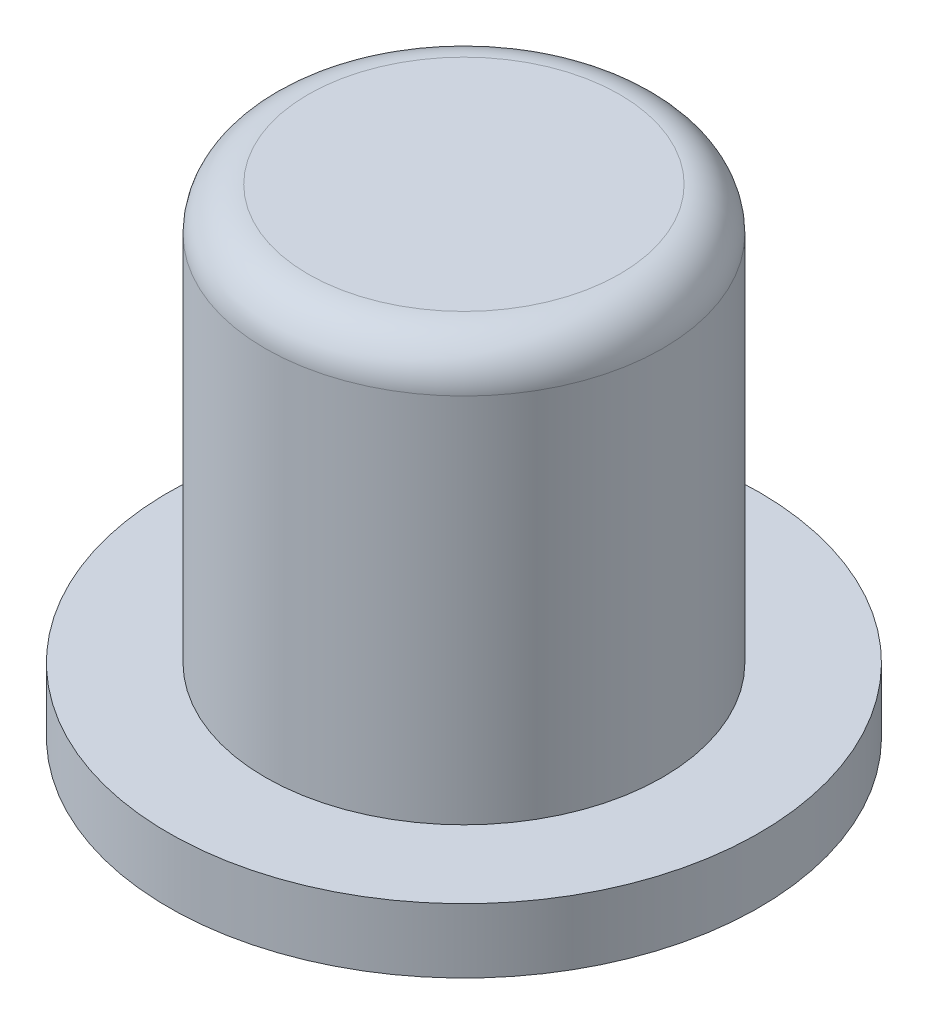
SolidWorks part; units mm, degrees
ref_plane "Face" through (0, 0, 0) normal (0, 0, 1) x (1, 0, 0)
ref_plane "Dessus" through (0, 0, 0) normal (0, 1, 0) x (1, 0, 0)
ref_plane "Droite" through (0, 0, 0) normal (1, 0, 0) x (0, 0, -1)
sketch "Sketch1" plane through (0, 0, 0) normal (0, 1, 0) x (1, 0, 0)
  circle A0 centre (0, 0) radius 3.4925
  dimension "D1" = 6.985
extrude "Boss-Extrude1" add sketch "Sketch1" along normal blind 0.762
sketch "Sketch2" plane through (0, 0.762, 0) normal (0, 1, 0) x (1, 0, 0)
  circle A0 centre (0, 0) radius 2.35
  dimension "D1" = 4.7
extrude "Boss-Extrude2" add sketch "Sketch2" along normal blind 4.9
fillet "Fillet1" radius 0.508 1 edges at (0, 5.662, 2.35)
